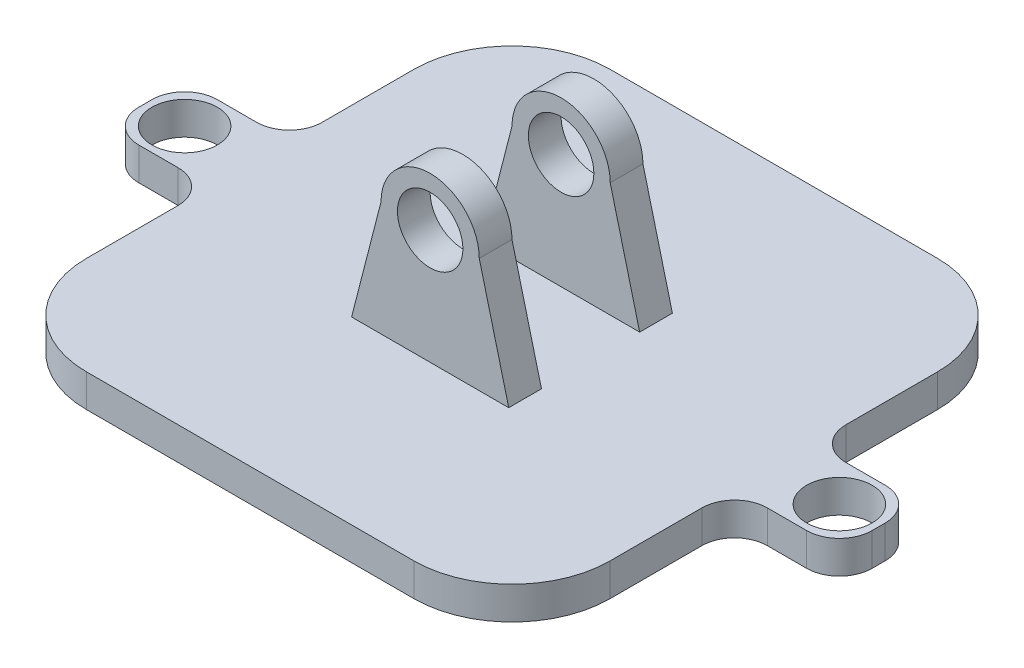
SolidWorks part; units mm, degrees
ref_plane "Front Plane" through (0, 0, 0) normal (0, 0, 1) x (1, 0, 0)
ref_plane "Top Plane" through (0, 0, 0) normal (0, 1, 0) x (1, 0, 0)
ref_plane "Right Plane" through (0, 0, 0) normal (1, 0, 0) x (0, 0, -1)
sketch "Sketch1" plane through (0, 0, 0) normal (0, 1, 0) x (1, 0, 0)
  line L0 (-40, 6) -> (-56, 6)
  line L1 (-25, 40) -> (25, 40)
  line L2 (-40, 25) -> (-40, 6)
  line L3 (-25, -40) -> (25, -40)
  line L4 (40, 25) -> (40, 6)
  line L5 (-40, -6) -> (-56, -6)
  line L6 (-56, 6) -> (-56, -6)
  line L7 (0, 0) -> (0, 25) construction
  line L8 (40, -6) -> (56, -6)
  line L9 (40, 6) -> (56, 6)
  line L10 (56, 6) -> (56, -6)
  line L11 (-40, -6) -> (-40, -25)
  line L12 (40, -6) -> (40, -25)
  arc A0 (25, 40) -> (40, 25) centre (25, 25) cw
  arc A1 (-40, -25) -> (-25, -40) centre (-25, -25) ccw
  arc A2 (-25, 40) -> (-40, 25) centre (-25, 25) ccw
  arc A3 (25, -40) -> (40, -25) centre (25, -25) ccw
  circle A4 centre (-50, 0) radius 5
  circle A5 centre (50, 0) radius 5
  point P0 (0, 0)
  point P8 (40, 40)
  point P11 (-40, -40)
  point P14 (-40, 40)
  dimension "D4" = 15
  dimension "D5" = 10
  dimension "D6" = 10
  dimension "D7" = 40
  dimension "D1" = 80
  dimension "D2" = 80
  dimension "D3" = 40
  dimension "D8" = 6
  dimension "D9" = 6
  dimension "D10" = 16
extrude "Boss-Extrude1" add sketch "Sketch1" along normal mid plane 5
fillet "Fillet1" radius 5 8 edges at (-40, 0, -6) (-56, 0, -6) (-56, 0, 6) (-40, 0, 6) (40, 0, -6) (56, 0, -6) (56, 0, 6) (40, 0, 6)
sketch "Sketch2" plane through (0, 0, 0) normal (0, 0, 1) x (1, 0, 0)
  line L0 (-7.5, 20) -> (-12, 2.5)
  line L1 (-25, 2.5) -> (25, 2.5) construction
  line L2 (7.5, 20) -> (12, 2.5)
  line L3 (-12, 2.5) -> (12, 2.5)
  arc A0 (7.5, 20) -> (-7.5, 20) centre (0, 20) ccw
  dimension "D1" = 15
  dimension "D2" = 20
  dimension "D3" = 12
  dimension "D4" = 12
extrude "Boss-Extrude2" add sketch "Sketch2" along normal mid plane 5 from offset 10
extrude "Boss-Extrude3" add sketch "Sketch2<2>" along normal mid plane 5 from offset 10 offset against normal yes
sketch "Sketch2<2>" plane through (0, 0, 0) normal (0, 0, 1) x (1, 0, 0) same geometry as "Sketch2"
sketch "Sketch3" plane through (0, 0, 12.5) normal (0, 0, 1) x (1, 0, 0)
  circle A0 centre (0, 20) radius 5
  dimension "D1" = 10
extrude "Cut-Extrude1" cut sketch "Sketch3" against normal blind 85
